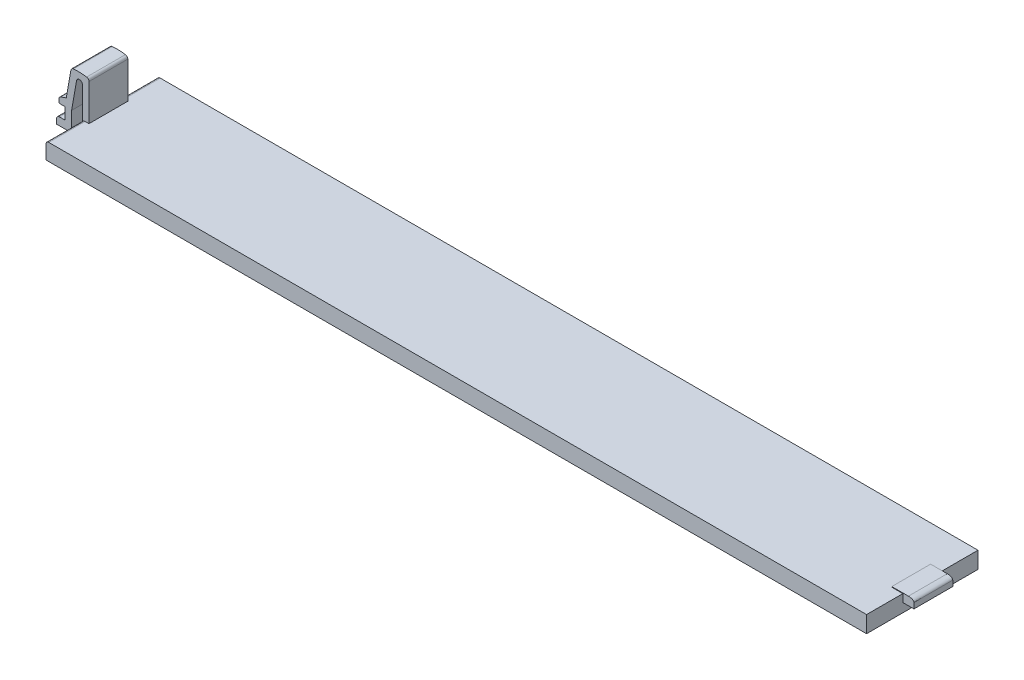
SolidWorks part; units mm, degrees
ref_plane "前视基准面" through (0, 0, 0) normal (0, 0, 1) x (1, 0, 0)
ref_plane "上视基准面" through (0, 0, 0) normal (0, 1, 0) x (1, 0, 0)
ref_plane "右视基准面" through (0, 0, 0) normal (1, 0, 0) x (0, 0, -1)
other "Configuration Table"
sketch "草图1" plane through (0, 0, 0) normal (0, 1, 0) x (1, 0, 0)
  line L1 (-74, 10.05) -> (74, 10.05)
  line L2 (-74, 10.05) -> (-74, -10.05)
  line L3 (-74, -10.05) -> (74, -10.05)
  line L4 (74, 10.05) -> (74, -10.05)
  line L5 (-74, 10.05) -> (74, -10.05) construction
  line L6 (-74, -10.05) -> (74, 10.05) construction
  point P0 (0, 0)
  dimension "D1" = 148
  dimension "D2" = 20.1
extrude "凸台-拉伸1" add sketch "草图1" along normal blind 3
sketch "草图2" plane through (0, 3, 0) normal (0, 1, 0) x (1, 0, 0)
  line L0 (74, -10.05) -> (74, 10.05) construction
  line L1 (72, 3.5) -> (76, 3.5)
  line L2 (72, 3.5) -> (72, -3.5)
  line L3 (72, -3.5) -> (76, -3.5)
  line L4 (76, 3.5) -> (76, -3.5)
  line L5 (74, 0) -> (63.5421, 0) construction
  dimension "D1" = 2
  dimension "D2" = 2
  dimension "D3" = 7
extrude "凸台-拉伸2" add sketch "草图2" along normal blind 1.5 from offset 1.4 offset against normal yes
sketch "草图5" plane through (0, 0, 10.05) normal (0, 0, 1) x (1, 0, 0)
  line L0 (-74, 3) -> (-74, 9)
  line L1 (-74.9616, 9.0287) -> (-75.9365, 3.5)
  line L3 (-76.894, 4.9803) -> (-75.989, 10.1127)
  line L4 (-72.8, 3) -> (-72.8, 10)
  line L5 (-74, 3) -> (74, 3) construction
  line L6 (-74, 0) -> (-75.5, 0) construction
  line L7 (-74, 3) -> (-74, 0) construction
  line L8 (-72.8, 3) -> (-74, 3)
  line L9 (-77.1365, 3.5) -> (-75.9365, 3.5) construction
  line L11 (-75.9365, 3.5) -> (-75.9365, 0)
  line L12 (91.1, 3) -> (-86.9, 3) construction
  line L13 (-77.1365, 3.5) -> (-77.1365, 1.4)
  line L14 (-77.2, 0) -> (-75.9365, 0)
  line L15 (-77.1365, 3.5) -> (-78.2365, 3.5)
  line L16 (-78.2365, 3.5) -> (-78.2365, 4.5)
  line L17 (-78.2365, 4.5) -> (-76.894, 4.9803)
  line L19 (-78.6365, 1.4) -> (-77.1365, 1.4)
  line L20 (-78.6365, 1.4) -> (-78.6365, 0)
  line L21 (-78.6365, 0) -> (-77.2, 0)
  arc A0 (-74.9616, 9.0287) -> (-74, 9) centre (-74.75, 0) cw
  arc A1 (-72.8, 10) -> (-75.989, 10.1127) centre (-74.75, 0) ccw
  dimension "D1" = 1.2
  dimension "D2" = 1.2
  dimension "D3" = 10
  dimension "D4" = 7
  dimension "D5" = 6
  dimension "D6" = 1.5
  dimension "D7" = 2
  dimension "D8" = 1.5
  dimension "D9" = 1
  dimension "D10" = 1.1
  dimension "D11" = 1.2
  dimension "D12" = 1.4
  dimension "D13" = 1.5
  dimension "D14" = 0.5
extrude "凸台-拉伸4" add sketch "草图5" along normal mid plane 7 from surface starting at plane "前视基准面"
fillet "圆角2" radius 0.5 1 edges at (76, 3.1, 0) second distance 1 first distance on face at (76, 2.35, 0)
sketch "草图6" plane through (-78.2365, 0, 0) normal (-1, 0, 0) x (0, 0, 1)
  line L1 (-1.5, 4.9803) -> (1.5, 4.9803)
  line L2 (-1.5, 4.9803) -> (-1.5, 3.5)
  line L3 (-1.5, 3.5) -> (1.5, 3.5)
  line L4 (1.5, 4.9803) -> (1.5, 3.5)
  line L5 (3.5, 3.5) -> (-3.5, 3.5) construction
  line L6 (3.5, 4.5) -> (3.5, 3.5) construction
  line L7 (-3.5, 4.5) -> (-3.5, 3.5) construction
  line L8 (3.5, 4.9803) -> (-3.5, 4.9803) construction
  dimension "D1" = 2
  dimension "D2" = 2
extrude "切除-拉伸1" cut sketch "草图6" against normal up to surface (1.3425 mm away) up to face at (-76.4415, 7.5465, 0)
fillet "圆角3" radius 0.5 9 edges at (-74, 9, 0) (-74.9616, 9.0287, 0) (-72.8, 10, 0) (-75.989, 10.1127, 0) (-78.6365, 1.4, 0) (-78.2365, 4.5, -2.5) (-78.2365, 4.5, 2.5) (-74, 3, -6.775) (-74, 3, 6.775)
fillet "圆角4" radius 0.2 2 edges at (-78.2365, 3.5, 2.5) (-78.2365, 3.5, -2.5)
